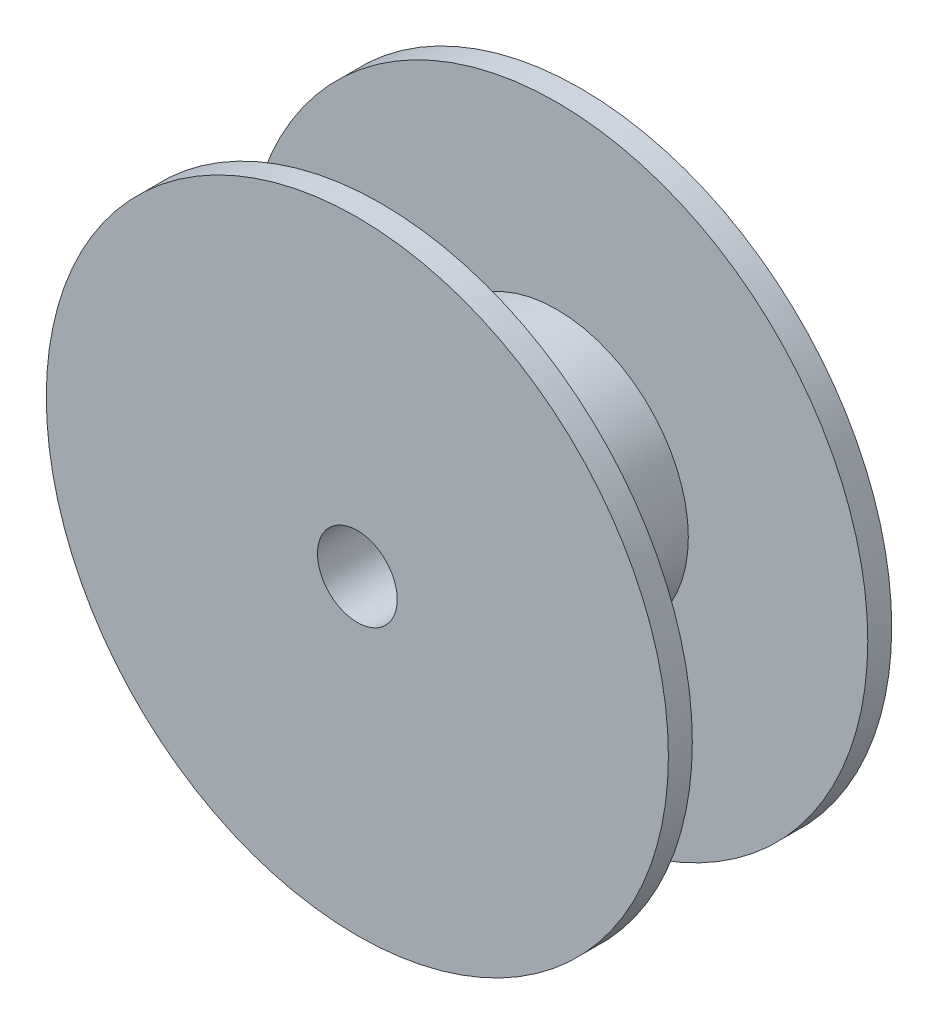
SolidWorks part; units mm, degrees
ref_plane "Front Plane" through (0, 0, 0) normal (0, 0, 1) x (1, 0, 0)
ref_plane "Top Plane" through (0, 0, 0) normal (0, 1, 0) x (1, 0, 0)
ref_plane "Right Plane" through (0, 0, 0) normal (1, 0, 0) x (0, 0, -1)
sketch "Sketch1" plane through (0, 0, 0) normal (0, 0, 1) x (1, 0, 0)
  circle A0 centre (0, 0) radius 99.06
  dimension "D1" = 198.12
extrude "Boss-Extrude1" add sketch "Sketch1" along normal blind 35.56 and the other way blind 35.56 contours A0
sketch "Sketch3" plane through (0, 0, 0) normal (0, 0, 1) x (1, 0, 0)
  circle A0 centre (0, 0) radius 41.91
  circle A1 centre (0, 0) radius 99.06 construction
  dimension "D1" = 57.15
extrude "Cut-Extrude1" cut sketch "Sketch3" against normal blind 27.94 and the other way blind 27.94 flip side to cut
sketch "Sketch4" plane through (0, 0, 0) normal (0, 0, 1) x (1, 0, 0)
  circle A0 centre (0, 0) radius 12.7
  dimension "D1" = 25.4
extrude "Cut-Extrude2" cut sketch "Sketch4" against normal through all and the other way through all
ref_axis "Axis1" through (0, 0, -35.56) along (0, 0, 1)
